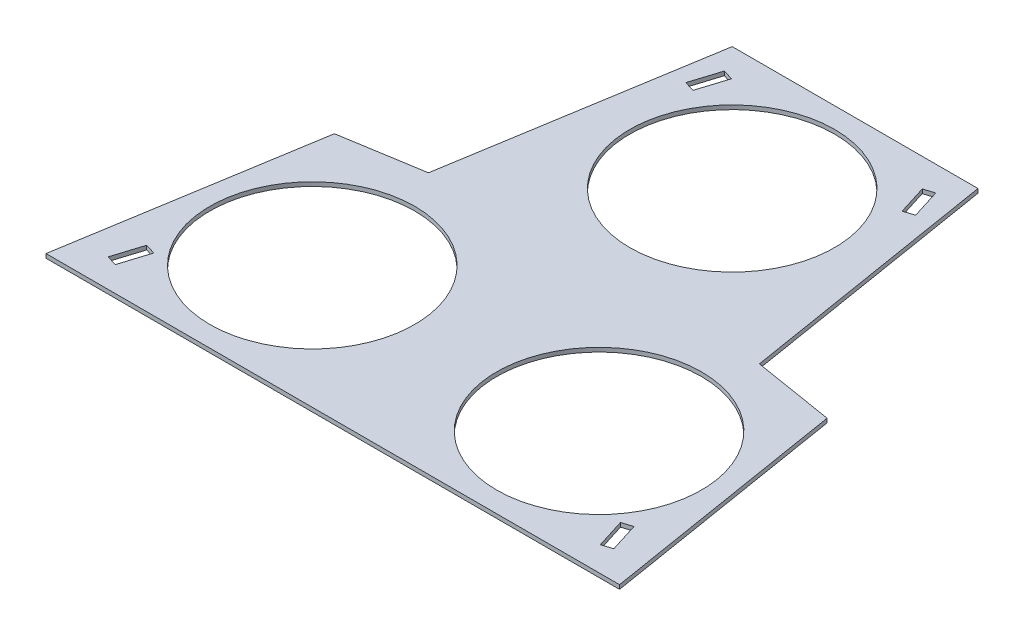
SolidWorks part; units mm, degrees
material "Acrylic (Medium-high impact)"
ref_plane "Front Plane" through (0, 0, 0) normal (0, 0, 1) x (1, 0, 0)
ref_plane "Top Plane" through (0, 0, 0) normal (0, 1, 0) x (1, 0, 0)
ref_plane "Right Plane" through (0, 0, 0) normal (1, 0, 0) x (0, 0, -1)
sketch "Sketch1" plane through (0, 0, 0) normal (0, 1, 0) x (1, 0, 0)
  line L0 (-140, 0) -> (140, 0)
  line L1 (140, 0) -> (120.264, 121.0641)
  line L2 (120.264, 121.0641) -> (80.7852, 127.5)
  line L3 (80.7852, 127.5) -> (60, 255)
  line L4 (-60, 255) -> (60, 255)
  line L6 (-60, 255) -> (-80.7852, 127.5)
  line L7 (-80.7852, 127.5) -> (-120.264, 121.0641)
  line L8 (-120.264, 121.0641) -> (-140, 0)
  line L9 (0, 0) -> (0, 255) construction
  circle A0 centre (0, 195) radius 50
  circle A1 centre (-70, 60) radius 50
  circle A2 centre (70, 60) radius 50
  dimension "D1" = 100
  dimension "D2" = 100
  dimension "D3" = 100
  dimension "D4" = 60
  dimension "D5" = 60
  dimension "D6" = 140
  dimension "D7" = 135
  dimension "D8" = 127.5
  dimension "D9" = 280
  dimension "D10" = 120
  dimension "D11" = 40
extrude "Boss-Extrude1" add sketch "Sketch1" along normal blind 2
sketch "Sketch2" plane through (0, 2, 0) normal (0, 1, 0) x (1, 0, 0)
  line L0 (0, 0) -> (0, 255) construction
  line L1 (60, 255) -> (-60, 255) construction
  line L2 (-125, 0) -> (-45, 255) construction
  line L3 (-56.0739, 228.4711) -> (-51.5838, 242.7833)
  line L4 (-140, 0) -> (140, 0) construction
  line L5 (-56.0739, 228.4711) -> (-51.0647, 226.8996)
  line L6 (-51.5838, 242.7833) -> (-46.5746, 241.2118)
  line L7 (-51.0647, 226.8996) -> (-46.5746, 241.2118)
  line L8 (-56.0739, 228.4711) -> (-46.5746, 241.2118) construction
  line L9 (-51.5838, 242.7833) -> (-51.0647, 226.8996) construction
  line L10 (113.9261, 26.5289) -> (123.4254, 13.7882) construction
  line L11 (-118.4162, 12.2167) -> (-113.9261, 26.5289)
  line L12 (-118.4162, 12.2167) -> (-123.4254, 13.7882)
  line L13 (-113.9261, 26.5289) -> (-118.9353, 28.1004)
  line L14 (-123.4254, 13.7882) -> (-118.9353, 28.1004)
  line L15 (-118.4162, 12.2167) -> (-118.9353, 28.1004) construction
  line L16 (-113.9261, 26.5289) -> (-123.4254, 13.7882) construction
  line L17 (118.4162, 12.2167) -> (118.9353, 28.1004) construction
  line L18 (51.5838, 242.7833) -> (51.0647, 226.8996) construction
  line L19 (56.0739, 228.4711) -> (46.5746, 241.2118) construction
  line L20 (125, 0) -> (45, 255) construction
  line L21 (123.4254, 13.7882) -> (118.9353, 28.1004)
  line L22 (113.9261, 26.5289) -> (118.9353, 28.1004)
  line L23 (118.4162, 12.2167) -> (123.4254, 13.7882)
  line L24 (118.4162, 12.2167) -> (113.9261, 26.5289)
  line L25 (51.0647, 226.8996) -> (46.5746, 241.2118)
  line L26 (51.5838, 242.7833) -> (46.5746, 241.2118)
  line L27 (56.0739, 228.4711) -> (51.0647, 226.8996)
  line L28 (56.0739, 228.4711) -> (51.5838, 242.7833)
  line L29 (-85, 127.5) -> (-208.5894, 166.2732) construction
  point P10 (-51.3242, 234.8415)
  point P13 (-118.6758, 20.1585)
  point P31 (118.6758, 20.1585)
  point P32 (51.3242, 234.8415)
  dimension "D1" = 15
  dimension "D2" = 15
  dimension "D3" = 5.25
  dimension "D4" = 15
  dimension "D5" = 210
extrude "Cut-Extrude1" cut sketch "Sketch2" against normal blind 5
